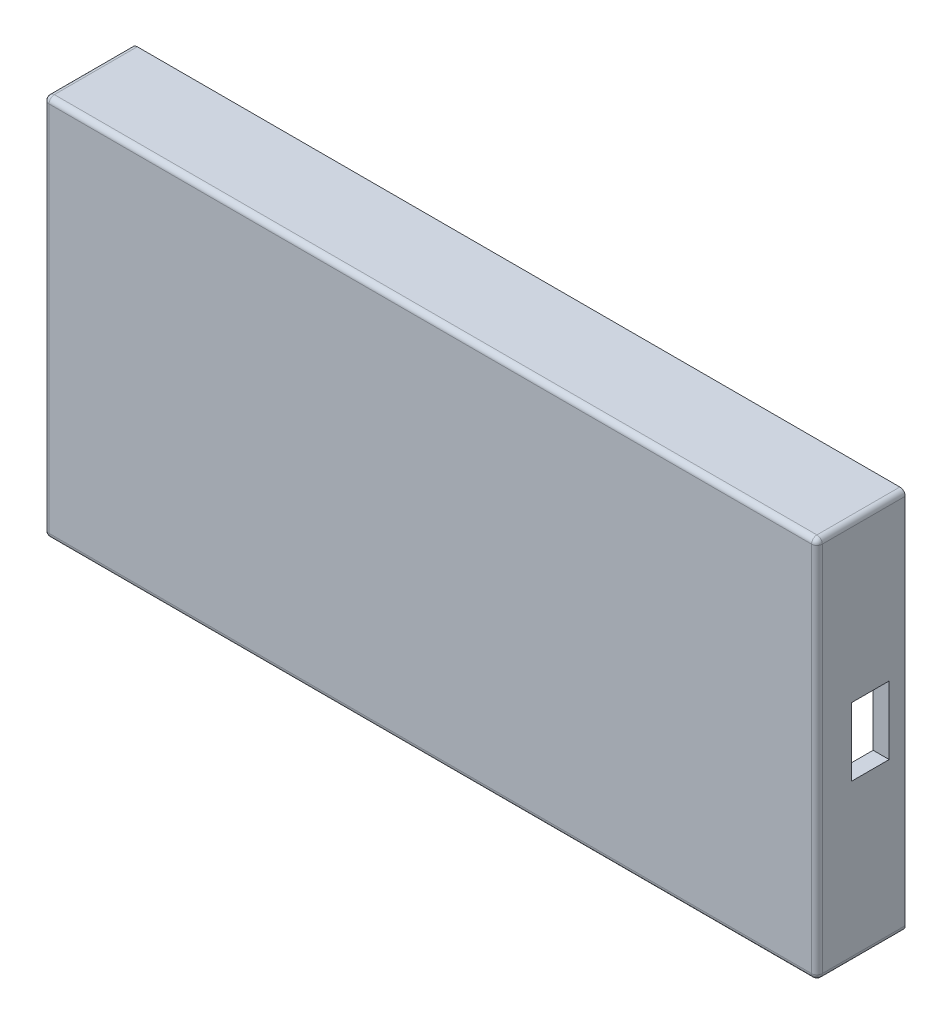
SolidWorks part; units mm, degrees
ref_plane "Plano frontal" through (0, 0, 0) normal (0, 0, 1) x (1, 0, 0)
ref_plane "Plano superior" through (0, 0, 0) normal (0, 1, 0) x (1, 0, 0)
ref_plane "Plano direito" through (0, 0, 0) normal (1, 0, 0) x (0, 0, -1)
sketch "Esboço2" plane through (0, 0, 0) normal (0, 0, 1) x (1, 0, 0)
  line L0 (66.7708, -1.788) -> (66.5169, -1.788)
  line L1 (65.8819, -1.153) -> (65.8819, 11.567)
  line L2 (66.5169, 12.202) -> (66.7709, 12.202)
  line L3 (67.4059, 12.837) -> (67.4059, 35.941)
  line L4 (66.3884, 36.957) -> (-34.1931, 36.957)
  line L5 (-34.8281, 36.3219) -> (-34.8281, 36.068)
  line L6 (-35.4632, 35.433) -> (-48.1831, 35.433)
  line L7 (-48.8181, 36.068) -> (-48.8181, 36.322)
  line L8 (-49.4532, 36.957) -> (-65.5631, 36.957)
  line L9 (-66.5791, 35.9396) -> (-66.5791, 18.923)
  line L10 (-66.5791, 18.923) -> (-69.1191, 16.383)
  line L11 (-69.1191, 16.383) -> (-69.1191, -16.383)
  line L12 (-69.1191, -16.383) -> (-66.5791, -18.923)
  line L13 (-66.5791, -18.923) -> (-66.5791, -25.527)
  line L14 (-65.5617, -26.543) -> (66.3899, -26.543)
  line L15 (67.4059, -25.5256) -> (67.4059, -2.423)
  circle A0 centre (-60.8641, 19.812) radius 1.8201
  circle A1 centre (-22.7641, 29.337) radius 1.6002
  circle A2 centre (1.3659, 14.097) radius 1.6002
  circle A3 centre (-29.1141, -18.923) radius 1.6002
  circle A4 centre (1.3659, -13.843) radius 1.6002
  circle A5 centre (52.1659, 29.337) radius 1.6002
  circle A6 centre (53.4359, -18.923) radius 1.7683
  arc A7 (67.4059, -2.423) -> (66.7708, -1.788) centre (66.7708, -2.423) ccw
  arc A8 (65.8819, -1.153) -> (66.5169, -1.788) centre (66.5169, -1.153) ccw
  arc A9 (66.5169, 12.202) -> (65.8819, 11.567) centre (66.5169, 11.567) ccw
  arc A10 (66.7709, 12.202) -> (67.4059, 12.837) centre (66.7708, 12.837) ccw
  arc A11 (67.4059, 35.941) -> (66.3884, 36.957) centre (66.3884, 35.9396) ccw
  arc A12 (-34.1931, 36.957) -> (-34.8281, 36.3219) centre (-34.1931, 36.3219) ccw
  arc A13 (-35.4632, 35.433) -> (-34.8281, 36.068) centre (-35.4632, 36.068) ccw
  arc A14 (-48.8181, 36.068) -> (-48.1831, 35.433) centre (-48.1831, 36.068) ccw
  arc A15 (-48.8181, 36.322) -> (-49.4532, 36.957) centre (-49.4532, 36.3219) ccw
  arc A16 (-65.5631, 36.957) -> (-66.5791, 35.9396) centre (-65.5617, 35.9396) ccw
  arc A17 (-66.5791, -25.527) -> (-65.5617, -26.543) centre (-65.5617, -25.5256) ccw
  arc A18 (66.3899, -26.543) -> (67.4059, -25.5256) centre (66.3884, -25.5256) ccw
extrude "Ressalto-extrusão1" add sketch "Esboço2" along normal blind 1.5
sketch "Arquivos locais1" plane through (0, 0, 0) normal (0, 0, -1) x (-1, 0, 0)
  line L2 (43.0791, -18.923) -> (43.0791, -25.527)
  line L3 (43.0791, -18.923) -> (43.0791, -25.527) construction
  line L4 (53.5791, -18.923) -> (53.5791, -25.527) construction
  line L5 (65.5617, -22.043) -> (-66.3899, -22.043)
  line L6 (65.5617, -22.043) -> (-66.3899, -22.043) construction
  line L7 (65.5617, -13.043) -> (-66.3899, -13.043) construction
  circle A0 centre (43.0791, -13.043) radius 1.5
  circle A1 centre (53.5791, -13.043) radius 1.5
  circle A2 centre (43.0791, -22.043) radius 1.5
  circle A5 centre (53.5791, -22.043) radius 1.5
  dimension "D5" = 3
  dimension "D1" = 23.5
  dimension "D2" = 4.5
  dimension "D3" = 10.5
  dimension "D4" = 9
sketch "Arquivos locais2" plane through (0, 0, 0) normal (0, 0, -1) x (-1, 0, 0)
  line L1 (66.5791, 36.957) -> (54.5791, 36.957) construction
  line L2 (66.5791, 36.957) -> (66.5791, 24.957) construction
  line L3 (66.5791, 24.957) -> (54.5791, 24.957) construction
  line L4 (54.5791, 36.957) -> (54.5791, 24.957) construction
  line L5 (54.5791, 24.957) -> (66.5791, 24.957)
  line L6 (54.5791, 24.957) -> (54.5791, 31.8918)
  line L7 (54.5791, 31.8918) -> (66.5791, 31.8918)
  line L8 (66.5791, 24.957) -> (66.5791, 31.8918)
  dimension "D1" = 12
  dimension "D2" = 12
sketch "Arquivos locais3" plane through (0, 0, 0) normal (0, 0, -1) x (-1, 0, 0)
  circle A0 centre (-52.1659, 29.337) radius 3
  circle A1 centre (-1.3659, 14.097) radius 3
  circle A2 centre (-1.3659, -13.843) radius 3
  circle A3 centre (22.7641, 29.337) radius 3
  circle A4 centre (-53.4359, -18.923) radius 3
  circle A5 centre (29.1141, -18.923) radius 3
  circle A6 centre (60.8641, 19.812) radius 3
  dimension "D1" = 6
extrude "Ressalto-extrusão4" add sketch "Arquivos locais3" along normal blind 5.5 and the other way up to surface (1.5 mm away) other way up to face at (53.7661, 29.337, 1.5)
sketch "Arquivos locais4" plane through (0, 0, -5.5) normal (0, 0, -1) x (-1, 0, 0)
  circle A0 centre (-52.1659, 29.337) radius 1.35
  circle A1 centre (-53.4359, -18.923) radius 1.35
  circle A2 centre (-1.3659, 14.097) radius 1.35
  circle A3 centre (22.7641, 29.337) radius 1.35
  circle A4 centre (60.8641, 19.812) radius 1.35
  circle A5 centre (29.1141, -18.923) radius 1.35
  circle A6 centre (-1.3659, -13.843) radius 1.35
  dimension "D1" = 2.7
extrude "Ressalto-extrusão5" add sketch "Arquivos locais4" along normal blind 1.5
sketch "Arquivos locais5" plane through (0, 0, 1.5) normal (0, 0, 1) x (1, 0, 0)
  line L1 (67.4059, 36.957) -> (-69.1191, 36.957)
  line L2 (67.4059, 36.957) -> (67.4059, -26.543)
  line L3 (67.4059, -26.543) -> (-69.1191, -26.543)
  line L4 (-69.1191, 36.957) -> (-69.1191, -26.543)
extrude "Ressalto-extrusão6" add sketch "Arquivos locais5" against normal up to surface (1.5 mm away) up to face at (-57.8641, 19.812, 0)
sketch "Arquivos locais6" plane through (0, 0, 1.5) normal (0, 0, 1) x (1, 0, 0)
  line L8 (-70.1191, -27.543) -> (68.4059, -27.543)
  line L9 (68.4059, -27.543) -> (68.4059, 37.957)
  line L10 (68.4059, 37.957) -> (-70.1191, 37.957)
  line L11 (-70.1191, 37.957) -> (-70.1191, -27.543)
  line L12 (-70.1191, -27.543) -> (68.4059, -27.543)
  line L13 (68.4059, -27.543) -> (68.4059, 37.957)
  line L14 (68.4059, 37.957) -> (-70.1191, 37.957)
  line L15 (-70.1191, 37.957) -> (-70.1191, -27.543)
  dimension "D1" = 1
extrude "Ressalto-extrusão7" add sketch "Arquivos locais6" against normal up to surface (1.5 mm away) up to face at (-57.8641, 19.812, 0)
sketch "Arquivos locais7" plane through (0, 0, 1.5) normal (0, 0, 1) x (1, 0, 0)
  line L0 (-73.1191, 40.957) -> (-73.1191, -30.543)
  line L1 (-70.1191, 37.957) -> (68.4059, 37.957)
  line L2 (-70.1191, 37.957) -> (-70.1191, -27.543)
  line L3 (-70.1191, -27.543) -> (68.4059, -27.543)
  line L4 (68.4059, 37.957) -> (68.4059, -27.543)
  line L5 (-73.1191, -30.543) -> (71.4059, -30.543)
  line L6 (71.4059, 40.957) -> (71.4059, -30.543)
  line L7 (-73.1191, 40.957) -> (71.4059, 40.957)
  dimension "D1" = 3
extrude "Ressalto-extrusão8" add sketch "Arquivos locais7" against normal blind 16.5
sketch "Arquivos locais8" plane through (0, 0, -12) normal (0, 0, -1) x (-1, 0, 0)
  line L0 (-65.8819, 11.567) -> (-74.2556, 11.567)
  line L1 (-74.2556, 11.567) -> (-74.2556, -1.153)
  line L2 (-74.2556, -1.153) -> (-65.8819, -1.153)
  line L3 (-65.8819, -1.153) -> (-65.8819, 11.567)
extrude "Corte-extrusão1" cut sketch "Arquivos locais8" against normal blind 7
sketch "Arquivos locais9" plane through (0, 0, -12) normal (0, 0, -1) x (-1, 0, 0)
  line L0 (73.1191, -30.543) -> (-71.4059, -30.543) construction
  line L1 (-67.4059, -30.543) -> (-57.3948, -30.543)
  line L2 (-67.4059, -30.543) -> (-67.4059, -22.043)
  line L3 (-67.4059, -22.043) -> (-57.3948, -22.043)
  line L4 (-57.3948, -30.543) -> (-57.3948, -22.043)
  line L5 (65.5617, -22.043) -> (-66.3899, -22.043) construction
sketch "Arquivos locais10" plane through (0, 0, -7) normal (0, 0, -1) x (-1, 0, 0)
  line L1 (-67.4059, -22.043) -> (-57.3948, -22.043)
  line L2 (-67.4059, -22.043) -> (-67.4059, -30.543)
  line L3 (-67.4059, -30.543) -> (-57.3948, -30.543)
  line L4 (-57.3948, -22.043) -> (-57.3948, -30.543)
extrude "Corte-extrusão2" cut sketch "Arquivos locais10" along normal blind 5
fillet "Filete1" radius 1 4 edges at (-73.1191, 40.957, -6.75) (-73.1191, -30.543, -6.75) (71.4059, -30.543, -6.75) (71.4059, 40.957, -6.75)
fillet "Filete2" radius 1 8 edges at (-72.8262, 40.6641, 1.5) (-0.8566, 40.957, 1.5) (71.113, 40.6641, 1.5) (71.4059, 5.207, 1.5) (71.113, -30.2501, 1.5) (-0.8566, -30.543, 1.5) (-72.8262, -30.2501, 1.5) (-73.1191, 5.207, 1.5)
fillet "Filete3" radius 2 11 edges at (-0.8566, -27.543, 0) (-70.1191, 5.207, 0) (-0.8566, 37.957, 0) (68.4059, 5.207, 0) (56.4359, -18.923, 0) (55.1659, 29.337, 0) (4.3659, -13.843, 0) (4.3659, 14.097, 0) (-26.1141, -18.923, 0) (-57.8641, 19.812, 0) (-19.7641, 29.337, 0)
fillet "Filete4" radius 1 8 edges at (67.8201, -26.9572, -0.5858) (-69.5334, -26.9572, -0.5858) (-69.5334, 37.3712, -0.5858) (67.8201, 37.3712, -0.5858) (68.4059, -27.543, -8.5) (-70.1191, -27.543, -8.5) (-70.1191, 37.957, -8.5) (68.4059, 37.957, -8.5)
